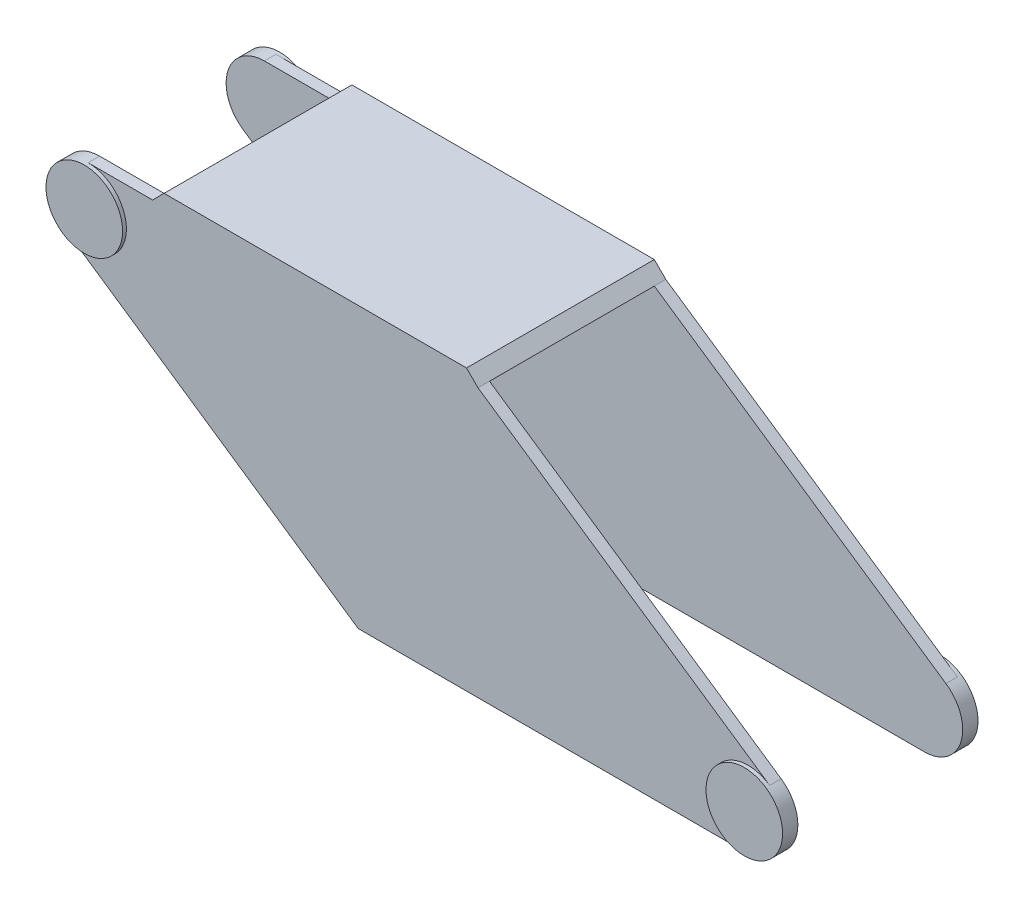
SolidWorks part; units mm, degrees
ref_plane "Alzado" through (0, 0, 0) normal (0, 0, 1) x (1, 0, 0)
ref_plane "Planta" through (0, 0, 0) normal (0, 1, 0) x (1, 0, 0)
ref_plane "Vista lateral" through (0, 0, 0) normal (1, 0, 0) x (0, 0, -1)
sketch "Croquis1" plane through (0, 0, 0) normal (0, 0, 1) x (1, 0, 0)
  line L0 (-69.745, 35.05) -> (32.1, 35.05)
  line L5 (32.1, 35.05) -> (108.2708, -16.7826)
  line L6 (102.645, -35.05) -> (0.8, -35.05)
  line L7 (0.8, -35.05) -> (-75.3708, 16.7826)
  circle A0 centre (-69.745, 25.05) radius 10
  circle A1 centre (102.645, -25.05) radius 10
  dimension "D2" = 20
  dimension "D3" = 172.39
  dimension "D1" = 20
  dimension "D4" = 101.845
  dimension "D5" = 25.05
  dimension "D6" = 102.645
  dimension "D7" = 34.234
extrude "Saliente-Extruir1" add sketch "Croquis1" along normal blind 3 contours A1 L5 L0 A0 L7 L6 region at (16.45, 0, 0)
extrude "Saliente-Extruir2" add sketch "Croquis1<3>" along normal blind 4 contours A0 | A1 region at (-69.745, 25.05, 0) region at (102.645, -25.05, 0)
sketch "Croquis1<3>" plane through (0, 0, 0) normal (0, 0, 1) x (1, 0, 0) same geometry as "Croquis1"
ref_plane "Plano1" through (0, 0, -21.525) normal (0, 0, -1) x (-1, 0, 0)
mirror "Simetría2" about plane through (0, 0, -21.525) normal (0, 0, -1) of bodies 102
sketch "Croquis2" plane through (0, 35.05, 0) normal (0, 1, 0) x (1, 0, 0)
  line L5 (38.555, 21.525) -> (-38.555, 21.525) construction
  line L6 (-52.9, -3) -> (32.1, -3)
  line L8 (-52.9, -3) -> (-52.9, 46.05)
  line L9 (-52.9, 46.05) -> (32.1, 46.05)
  line L10 (32.1, -3) -> (32.1, 46.05)
  line L11 (-52.9, -3) -> (32.1, 46.05) construction
  line L12 (-52.9, 46.05) -> (32.1, -3) construction
  point P0 (-10.4, 21.525)
  dimension "D1" = 85
extrude "Saliente-Extruir4" add sketch "Croquis2" along normal blind 3
chamfer "Chaflán3" distance 3 angle 45 1 edges at (32.1, 38.05, -21.525)
chamfer "Chaflán4" distance 3 angle 45 1 edges at (-52.9, 38.05, -21.525)
